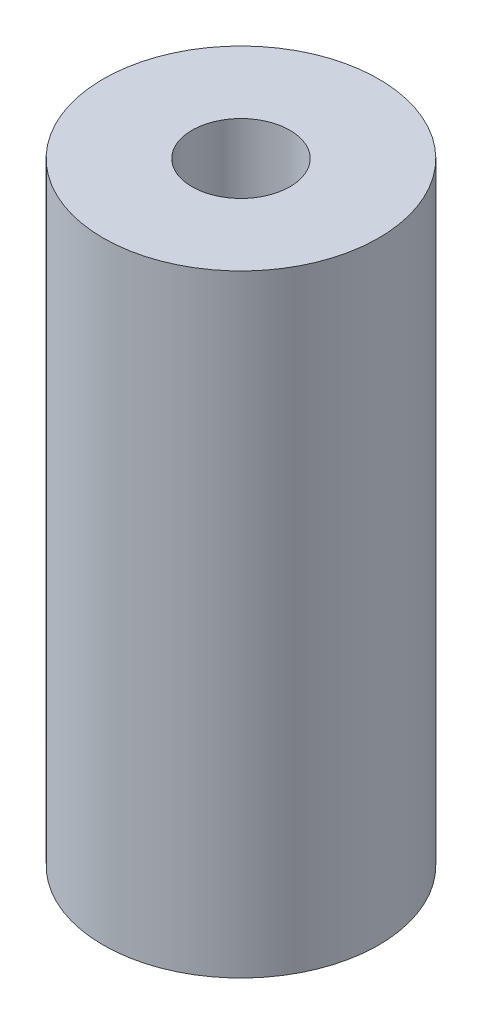
SolidWorks part; units mm, degrees
material "ABS"
ref_plane "Front Plane" through (0, 0, 0) normal (0, 0, 1) x (1, 0, 0)
ref_plane "Top Plane" through (0, 0, 0) normal (0, 1, 0) x (1, 0, 0)
ref_plane "Right Plane" through (0, 0, 0) normal (1, 0, 0) x (0, 0, -1)
sketch "Sketch1" plane through (0, 0, 0) normal (0, 1, 0) x (1, 0, 0)
  circle A0 centre (0, 0) radius 2.25
  dimension "D1" = 4.5
extrude "Boss-Extrude1" add sketch "Sketch1" along normal blind 10
sketch "Sketch2" plane through (0, 10, 0) normal (0, 1, 0) x (1, 0, 0)
  point P0 (0, 0)
hole_wizard "M2x0.4 Tapped Hole1" positions "Sketch2" profile "Sketch3" tap size "M2x0.4" standard "ANSI Metric" end condition through all
sketch "Sketch3" plane through (0, 10, 0) normal (1, 0, 0) x (0, 0, 1)
  line L0 (0, 0) -> (0, 10)
  line L1 (0, 10) -> (0.8, 10)
  line L2 (0.8, 10) -> (0.8, 0)
  line L5 (0.8, 0) -> (0, 0)
  line L11 (0, -6.35) -> (0, 107.95) construction
  dimension "Thru Tap Drill Dia." = 1.6
  dimension "Thru Tap Drill Depth" = 10
